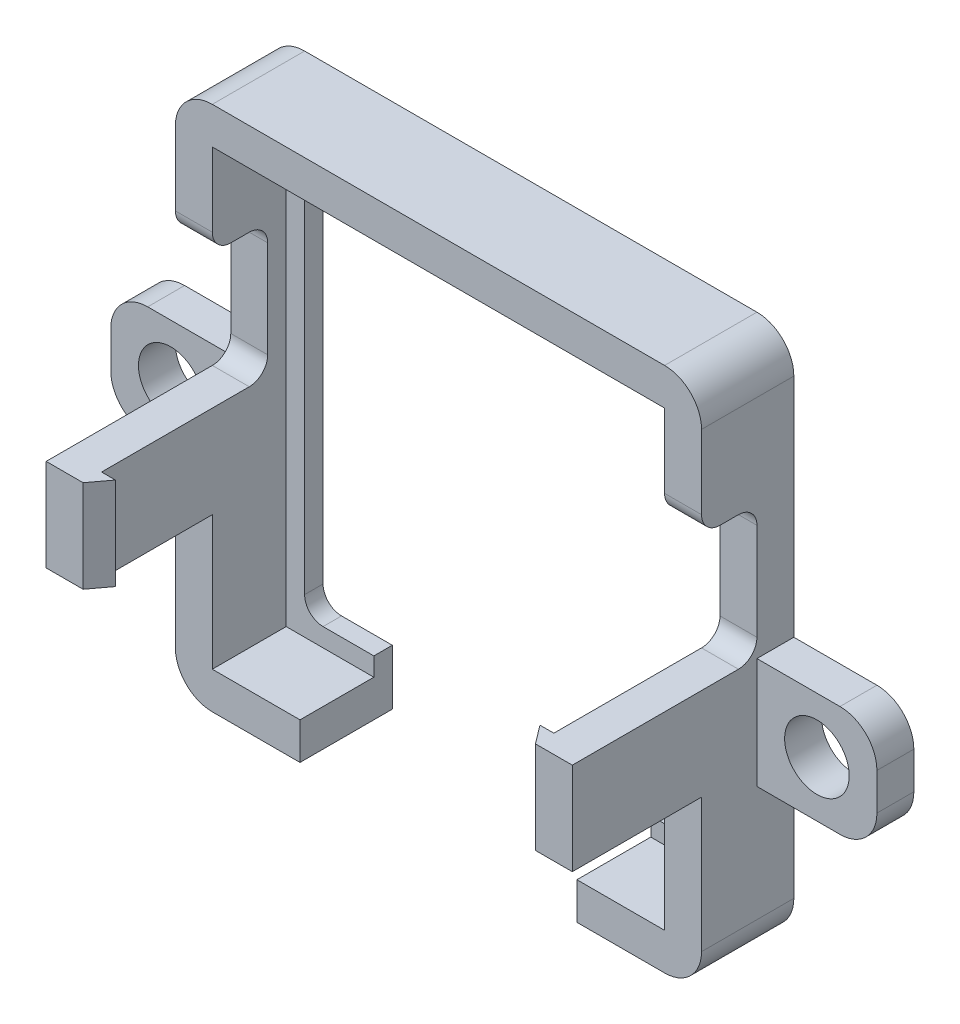
SolidWorks part; units mm, degrees
ref_plane "正面" through (0, 0, 0) normal (0, 0, 1) x (1, 0, 0)
ref_plane "平面" through (0, 0, 0) normal (0, 1, 0) x (1, 0, 0)
ref_plane "右側面" through (0, 0, 0) normal (1, 0, 0) x (0, 0, -1)
sketch "ｽｹｯﾁ1" plane through (0, 0, 0) normal (0, 0, 1) x (1, 0, 0)
  line L0 (-14.25, 14.25) -> (14.25, 14.25)
  line L1 (-12.25, 12.25) -> (12.25, 12.25)
  line L2 (-12.25, 12.25) -> (-12.25, -12.25)
  line L3 (-12.25, -12.25) -> (12.25, -12.25)
  line L4 (12.25, 12.25) -> (12.25, -12.25)
  line L5 (-12.25, 12.25) -> (12.25, -12.25) construction
  line L6 (-12.25, -12.25) -> (12.25, 12.25) construction
  line L7 (14.25, 14.25) -> (14.25, -14.25)
  line L8 (-14.25, -14.25) -> (14.25, -14.25)
  line L9 (-14.25, 14.25) -> (-14.25, -14.25)
  point P0 (0, 0)
  dimension "D1" = 24.5
  dimension "D2" = 2
  dimension "24.5" = 24.5
extrude "ﾎﾞｽ - 押し出し1" add sketch "ｽｹｯﾁ1" along normal blind 4 contours L0 L9 L8 L7 L1 L4 L3 L2 region at (0, 13.8469, 0)
sketch "ｽｹｯﾁ2" plane through (0, -14.25, 0) normal (0, -1, 0) x (-1, 0, 0)
  line L0 (0, 0) -> (0, -4) construction
  line L1 (14.25, -4) -> (-14.25, -4) construction
  line L3 (7.5, 0) -> (-7.5, 0)
  line L4 (7.5, 0) -> (7.5, -4)
  line L5 (7.5, -4) -> (-7.5, -4)
  line L6 (-7.5, 0) -> (-7.5, -4)
  line L7 (7.5, 0) -> (-7.5, -4) construction
  line L8 (7.5, -4) -> (-7.5, 0) construction
  point P5 (0, -2)
  dimension "D1" = 15
extrude "ｶｯﾄ - 押し出し1" cut sketch "ｽｹｯﾁ2" against normal up to next
sketch "ｽｹｯﾁ3" plane through (0, 0, 0) normal (0, 0, -1) x (-1, 0, 0)
  line L0 (-7.5, -11.25) -> (-10.25, -11.25)
  line L1 (-11.25, -10.25) -> (-11.25, 10.25)
  line L2 (-10.25, 11.25) -> (10.25, 11.25)
  line L3 (11.25, 10.25) -> (11.25, -10.25)
  line L4 (10.25, -11.25) -> (7.5, -11.25)
  line L5 (-7.5, -12.25) -> (-7.5, -11.25)
  line L6 (7.5, -12.25) -> (7.5, -11.25)
  line L12 (12.25, -12.25) -> (7.5, -12.25)
  line L13 (7.5, -12.25) -> (7.5, -14.25)
  line L14 (7.5, -14.25) -> (14.25, -14.25)
  line L15 (14.25, -14.25) -> (14.25, 14.25)
  line L16 (14.25, 14.25) -> (-14.25, 14.25)
  line L17 (-14.25, 14.25) -> (-14.25, -14.25)
  line L18 (-14.25, -14.25) -> (-7.5, -14.25)
  line L19 (-7.5, -14.25) -> (-7.5, -12.25)
  line L20 (-7.5, -12.25) -> (-12.25, -12.25)
  line L21 (-12.25, -12.25) -> (-12.25, 12.25)
  line L22 (-12.25, 12.25) -> (12.25, 12.25)
  line L23 (12.25, 12.25) -> (12.25, -12.25)
  line L24 (10.25, -12.25) -> (7.5, -12.25)
  line L25 (7.5, -12.25) -> (7.5, -14.25)
  line L26 (7.5, -14.25) -> (14.25, -14.25)
  line L27 (14.25, -14.25) -> (14.25, 14.25)
  line L28 (14.25, 14.25) -> (-14.25, 14.25)
  line L29 (-14.25, 14.25) -> (-14.25, -14.25)
  line L30 (-14.25, -14.25) -> (-7.5, -14.25)
  line L31 (-7.5, -14.25) -> (-7.5, -12.25)
  line L32 (-7.5, -12.25) -> (-10.25, -12.25)
  line L33 (-12.25, -10.25) -> (-12.25, 10.25)
  line L34 (-10.25, 12.25) -> (10.25, 12.25)
  line L35 (12.25, 10.25) -> (12.25, -10.25)
  arc A0 (10.25, 12.25) -> (12.25, 10.25) centre (10.25, 10.25) cw
  arc A1 (-12.25, 10.25) -> (-10.25, 12.25) centre (-10.25, 10.25) cw
  arc A2 (-10.25, -12.25) -> (-12.25, -10.25) centre (-10.25, -10.25) cw
  arc A3 (10.25, -12.25) -> (12.25, -10.25) centre (10.25, -10.25) ccw
  arc A4 (-10.25, -11.25) -> (-11.25, -10.25) centre (-10.25, -10.25) cw
  arc A5 (-11.25, 10.25) -> (-10.25, 11.25) centre (-10.25, 10.25) cw
  arc A6 (10.25, 11.25) -> (11.25, 10.25) centre (10.25, 10.25) cw
  arc A7 (10.25, -11.25) -> (11.25, -10.25) centre (10.25, -10.25) ccw
  line M17 (12.25, -12.25) -> (7.5, -12.25)
  line M18 (7.5, -12.25) -> (7.5, -14.25)
  line M19 (7.5, -14.25) -> (14.25, -14.25)
  line M20 (14.25, -14.25) -> (14.25, 14.25)
  line M21 (14.25, 14.25) -> (-14.25, 14.25)
  line M22 (-14.25, 14.25) -> (-14.25, -14.25)
  line M23 (-14.25, -14.25) -> (-7.5, -14.25)
  line M24 (-7.5, -14.25) -> (-7.5, -12.25)
  line M25 (-7.5, -12.25) -> (-12.25, -12.25)
  line M26 (-12.25, -12.25) -> (-12.25, 12.25)
  line M27 (-12.25, 12.25) -> (12.25, 12.25)
  line M28 (12.25, 12.25) -> (12.25, -12.25)
  dimension "D2" = 2
  dimension "D1" = 0
  dimension "D3" = 1
extrude "ﾎﾞｽ - 押し出し2" add sketch "ｽｹｯﾁ3" along normal blind 1 contours M28 M17 M18 M19 M20 M21 M22 M23 M24 M25 M26 M27 | A3 M17 M28 | A7 L4 L6 A3 A0 A1 A2 L5 L0 A4 L1 A5 L2 A6 L3 M17 M28 M27 M26 M25 | A2 M25 M26 | A1 M26 M27 | A0 M27 M28 region at (7.8465, -11.75, 0) region at (7.9031, -13.25, 0) region at (11.8033, -11.8033, 0) region at (11.8033, 11.8033, 0) region at (-11.8033, 11.8033, 0) region at (-11.8033, -11.8033, 0)
sketch "ｽｹｯﾁ4" plane through (0, 0, 4) normal (0, 0, 1) x (1, 0, 0)
  line L0 (12.25, -2.61) -> (-12.25, -2.61) construction
  line L3 (12.25, 12.25) -> (12.25, -12.25) construction
  line L5 (-12.25, 12.25) -> (-12.25, -12.25) construction
  line L6 (14.25, 14.25) -> (14.25, -14.25) construction
  line L7 (14.25, 0) -> (12.25, 0)
  line L12 (14.25, 0) -> (14.25, -5)
  line L13 (14.25, -5) -> (12.25, -5)
  line L18 (12.25, 0) -> (12.25, -5)
  line L19 (0, -6.6) -> (0, 6.6) construction
  line L20 (-14.25, -5) -> (-12.25, -5)
  line L21 (-12.25, 0) -> (-12.25, -5)
  line L22 (-14.25, 0) -> (-12.25, 0)
  line L23 (-14.25, 0) -> (-14.25, -5)
  dimension "D1" = 2.61
  dimension "D2" = 2.61
  dimension "D3" = 2.39
extrude "ﾎﾞｽ - 押し出し3" add sketch "ｽｹｯﾁ4" along normal blind 7
sketch "ｽｹｯﾁ5" plane through (0, 0, 0) normal (0, 1, 0) x (1, 0, 0)
  line L0 (12.25, -11) -> (11.5, -10)
  line L1 (11.5, -10) -> (12.25, -10)
  line L3 (12.25, -11) -> (12.25, -10)
  line L4 (0, -6.6) -> (0, 6.6) construction
  line L5 (-12.25, -11) -> (-11.5, -10)
  line L6 (-12.25, -11) -> (-12.25, -10)
  line L7 (-11.5, -10) -> (-12.25, -10)
  line L8 (12.25, -11) -> (12.25, -4) construction
  point P11 (12, -10)
  dimension "D1" = 1
  dimension "0.5" = 0.75
extrude "ﾎﾞｽ - 押し出し7" add sketch "ｽｹｯﾁ5" against normal up to surface (5 mm away) up to face at (13.25, -5, 7.5)
sketch "ｽｹｯﾁ6" plane through (0, 0, -1) normal (0, 0, -1) x (-1, 0, 0)
  line L0 (14.25, -3.0876) -> (-14.25, -3.0876) construction
  line L3 (0, 11.25) -> (0, -11.4252) construction
  line L4 (20.75, -6) -> (14.25, -6)
  line L5 (-20.75, 0) -> (-14.25, 0)
  line L6 (-20.75, 0) -> (-20.75, -6)
  line L7 (-20.75, -6) -> (-14.25, -6)
  line L8 (-14.25, 0) -> (-14.25, -6)
  line L9 (-20.75, 0) -> (-14.25, -6) construction
  line L10 (-20.75, -6) -> (-14.25, 0) construction
  line L11 (14.25, 0) -> (14.25, -6)
  line L12 (20.75, 0) -> (14.25, 0)
  line L13 (20.75, 0) -> (20.75, -6)
  line L15 (-10.25, 11.25) -> (10.25, 11.25) construction
  line L16 (-14.25, 14.25) -> (-14.25, -14.25) construction
  line L17 (14.25, -14.25) -> (14.25, 14.25) construction
  circle A0 centre (17.5, -3) radius 1.75
  circle A1 centre (-17.5, -3) radius 1.75
  point P2 (0, -0.0876)
  dimension "D1" = 3.5
  dimension "D2" = 35
  dimension "D3" = 6
  dimension "D4" = 3
extrude "ﾎﾞｽ - 押し出し6" add sketch "ｽｹｯﾁ6" against normal blind 2
fillet "ﾌｨﾚｯﾄ1" radius 2 8 edges at (-14.25, 14.25, 1.5) (-14.25, -14.25, 1.5) (14.25, -14.25, 1.5) (14.25, 14.25, 1.5) (20.75, 0, 0) (20.75, -6, 0) (-20.75, 0, 0) (-20.75, -6, 0)
sketch "ｽｹｯﾁ8" plane through (-14.25, 0, 0) normal (-1, 0, 0) x (0, 0, 1)
  line L0 (4, 12.25) -> (4, 0) construction
  line L1 (4, 7.25) -> (1, 7.25)
  line L2 (4, 7.25) -> (4, 0)
  line L3 (4, 0) -> (1, 0)
  line L4 (1, 7.25) -> (1, 0)
  line L5 (4, 12.25) -> (-1, 12.25) construction
  point P8 (4, 0)
  dimension "D1" = 3
  dimension "D2" = 5
extrude "ｶｯﾄ - 押し出し3" cut sketch "ｽｹｯﾁ8" against normal through all
fillet "ﾌｨﾚｯﾄ2" radius 1 6 edges at (-13.25, 0, 1) (-13.25, 7.25, 1) (-13.25, 7.25, 4) (13.25, 0, 1) (13.25, 7.25, 1) (13.25, 7.25, 4)
